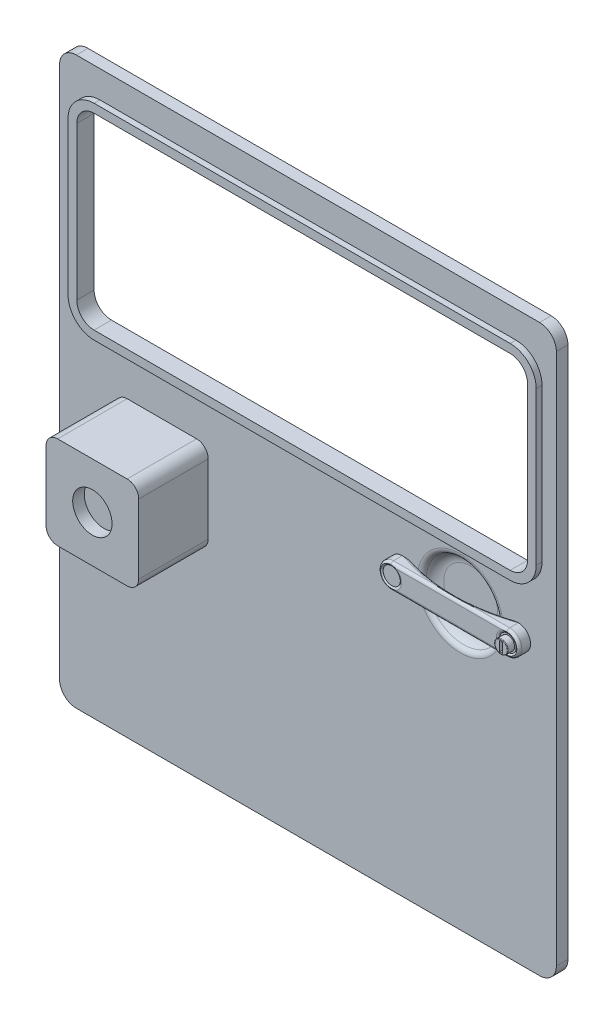
SolidWorks part; units mm, degrees
material "AISI 347 Annealed Stainless Steel (SS)"
ref_plane "Front Plane" through (0, 0, 0) normal (0, 0, 1) x (1, 0, 0)
ref_plane "Top Plane" through (0, 0, 0) normal (0, 1, 0) x (1, 0, 0)
ref_plane "Right Plane" through (0, 0, 0) normal (1, 0, 0) x (0, 0, -1)
sketch "Sketch1" plane through (0, 0, 0) normal (0, 0, 1) x (1, 0, 0)
  line L0 (400, 489.5011) -> (-400, 489.5011)
  line L1 (430, -459.5316) -> (430, 459.5316)
  line L2 (-400, -489.5011) -> (400, -489.5011)
  line L3 (-430, 459.5316) -> (-430, -459.5316)
  line L4 (400, 488.5011) -> (-400, 488.5011)
  line L5 (-429, 459.5316) -> (-429, -459.5316)
  line L6 (-400, -488.5011) -> (400, -488.5011)
  line L7 (429, -459.5316) -> (429, 459.5316)
  ellipse E0 centre (400, 459.5316) end of major axis (370, 459.5316) minor radius 29.9695 (430, 459.5316) -> (400, 489.5011) ccw
  ellipse E1 centre (400, -459.5316) end of major axis (430, -459.5316) minor radius 29.9695 (400, -489.5011) -> (430, -459.5316) ccw
  ellipse E2 centre (-400, -459.5316) end of major axis (-370, -459.5316) minor radius 29.9695 (-430, -459.5316) -> (-400, -489.5011) ccw
  ellipse E3 centre (-400, 459.5316) end of major axis (-370, 459.5316) minor radius 29.9695 (-400, 489.5011) -> (-430, 459.5316) ccw
  spline S0 degree 1 poles (-400, 488.5011) (-429, 459.5316) knots 0 0 1 1 construction
  spline S1 degree 1 poles (-429, -459.5316) (-400, -488.5011) knots 0 0 1 1 construction
  spline S2 degree 1 poles (400, -488.5011) (429, -459.5316) knots 0 0 1 1 construction
  spline S3 degree 1 poles (429, 459.5316) (400, 488.5011) knots 0 0 1 1 construction
  spline S4 degree 3 poles (-400, 488.5011) (-401.895, 488.5011) (-405.6955, 488.1273) (-412.9948, 485.9167) (-421.0414, 480.5501) (-426.4132, 472.512) (-428.6259, 465.2207) (-429, 461.4246) (-429, 459.5316) knots 1.570796 1.570796 1.570796 1.570796 1.767146 1.963495 2.356194 2.748894 2.945243 3.141593 3.141593 3.141593 3.141593
  spline S5 degree 3 poles (-429, -459.5316) (-429, -461.4246) (-428.6259, -465.2207) (-426.4132, -472.512) (-421.0414, -480.5501) (-412.9948, -485.9167) (-405.6955, -488.1273) (-401.895, -488.5011) (-400, -488.5011) knots 3.141593 3.141593 3.141593 3.141593 3.337942 3.534292 3.926991 4.31969 4.516039 4.712389 4.712389 4.712389 4.712389
  spline S6 degree 3 poles (400, -488.5011) (401.895, -488.5011) (405.6955, -488.1273) (412.9948, -485.9167) (421.0414, -480.5501) (426.4132, -472.512) (428.6259, -465.2207) (429, -461.4246) (429, -459.5316) knots -1.570796 -1.570796 -1.570796 -1.570796 -1.374447 -1.178097 -0.785398 -0.392699 -0.19635 0 0 0 0
  spline S7 degree 3 poles (429, 459.5316) (429, 461.4246) (428.6259, 465.2207) (426.4132, 472.512) (421.0414, 480.5501) (412.9948, 485.9167) (405.6955, 488.1273) (401.895, 488.5011) (400, 488.5011) knots -3.141593 -3.141593 -3.141593 -3.141593 -2.945243 -2.748894 -2.356194 -1.963495 -1.767146 -1.570796 -1.570796 -1.570796 -1.570796
  dimension "D1" = 1
extrude "Boss-Extrude1" add sketch "Sketch1" along normal mid plane 20 contours L7 S7 L4 S4 L5 S5 L6 S6
sketch "Sketch2" plane through (0, 0, 10) normal (0, 0, 1) x (1, 0, 0)
  line L0 (0, 488.5011) -> (0, 264.5322) construction
  line L1 (400, 488.5011) -> (-400, 488.5011) construction
  line L3 (359.2197, 102.3905) -> (-359.2197, 102.3905)
  line L4 (389.2197, 132.3905) -> (389.2197, 396.6739)
  line L5 (359.2197, 426.6739) -> (-359.2197, 426.6739)
  line L6 (-389.2197, 132.3905) -> (-389.2197, 396.6739)
  line L7 (389.2197, 102.3905) -> (-389.2197, 426.6739) construction
  line L8 (389.2197, 426.6739) -> (-389.2197, 102.3905) construction
  arc A0 (-359.2197, 102.3905) -> (-389.2197, 132.3905) centre (-359.2197, 132.3905) cw
  arc A1 (389.2197, 396.6739) -> (359.2197, 426.6739) centre (359.2197, 396.6739) ccw
  arc A2 (359.2197, 102.3905) -> (389.2197, 132.3905) centre (359.2197, 132.3905) ccw
  arc A3 (-359.2197, 426.6739) -> (-389.2197, 396.6739) centre (-359.2197, 396.6739) ccw
  dimension "D1" = 30
extrude "Cut-Extrude1" cut sketch "Sketch2" against normal through all
sketch "Sketch4" plane through (0, 0, 10) normal (0, 0, 1) x (1, 0, 0)
  line L1 (-192.2469, -141.7056) -> (-312.2469, -141.7056)
  line L2 (-172.2469, -121.7056) -> (-172.2469, -1.7056)
  line L3 (-192.2469, 18.2944) -> (-312.2469, 18.2944)
  line L4 (-332.2469, -121.7056) -> (-332.2469, -1.7056)
  line L5 (-172.2469, -141.7056) -> (-332.2469, 18.2944) construction
  line L6 (-172.2469, 18.2944) -> (-332.2469, -141.7056) construction
  arc A0 (-312.2469, -141.7056) -> (-332.2469, -121.7056) centre (-312.2469, -121.7056) cw
  arc A1 (-172.2469, -1.7056) -> (-192.2469, 18.2944) centre (-192.2469, -1.7056) ccw
  arc A2 (-192.2469, -141.7056) -> (-172.2469, -121.7056) centre (-192.2469, -121.7056) ccw
  arc A3 (-312.2469, 18.2944) -> (-332.2469, -1.7056) centre (-312.2469, -1.7056) ccw
  point P0 (-252.2469, -61.7056)
  point P5 (-252.2469, -61.7056)
  dimension "D3" = 20
  dimension "D1" = 160
  dimension "D2" = 160
extrude "Boss-Extrude2" add sketch "Sketch4" along normal blind 120
sketch "Sketch5" plane through (0, 0, 130) normal (0, 0, 1) x (1, 0, 0)
  line L0 (-252.2469, 18.2944) -> (-252.2469, -141.7056) construction
  line L1 (-192.2469, 18.2944) -> (-312.2469, 18.2944) construction
  line L2 (-312.2469, -141.7056) -> (-192.2469, -141.7056) construction
  circle A0 centre (-252.2469, -61.7056) radius 33.9854
extrude "Cut-Extrude2" cut sketch "Sketch5" against normal blind 20
sketch "Sketch6" plane through (0, 0, 10) normal (0, 0, 1) x (1, 0, 0)
  line L0 (162.7399, 0) -> (363.4525, 0) construction
  line L1 (162.7399, 21.0206) -> (363.4525, 21.0206)
  line L2 (162.7399, -21.0206) -> (363.4525, -21.0206)
  arc A0 (162.7399, 21.0206) -> (162.7399, -21.0206) centre (162.7399, 0) ccw
  arc A1 (363.4525, -21.0206) -> (363.4525, 21.0206) centre (363.4525, 0) ccw
  point P3 (263.0962, 0)
  point P8 (162.7399, 0)
  point P9 (363.4525, 0)
extrude "Boss-Extrude3" add sketch "Sketch6" along normal blind 20
sketch "Sketch9" plane through (0, 0, 10) normal (0, 0, 1) x (1, 0, 0)
  line L0 (263.0962, 21.0206) -> (263.0962, -21.0206) construction
  line L1 (363.4525, 21.0206) -> (162.7399, 21.0206) construction
  line L2 (162.7399, -21.0206) -> (363.4525, -21.0206) construction
  circle A0 centre (263.0962, 0) radius 66.5209
extrude "Cut-Extrude5" cut sketch "Sketch9" against normal blind 18
sketch "Sketch10" plane through (0, 21.0206, 0) normal (0, 1, 0) x (1, 0, 0)
  line L0 (199.9839, -10) -> (162.7399, -10) construction
  line L1 (363.4525, -10) -> (326.2085, -10) construction
  line L2 (181.3619, -10) -> (348.7014, -10)
  arc A0 (181.3619, -10) -> (348.7014, -10) centre (265.0317, 269.1036) ccw
  point P3 (348.7014, -10)
extrude "Cut-Extrude6" cut sketch "Sketch10" against normal blind 60
fillet "Fillet1" radius 20 1 edges at (329.6171, 0, -8)
fillet "Fillet2" radius 10 1 edges at (329.6171, 0, 10)
sketch "Sketch11" plane through (0, 0, 30) normal (0, 0, 1) x (1, 0, 0)
  circle A0 centre (162.7399, 0) radius 14.8405
  circle A1 centre (363.4525, 0) radius 14.252
extrude "Cut-Extrude7" cut sketch "Sketch11" against normal blind 2
sketch "Sketch12" plane through (0, 0, 28) normal (0, 0, 1) x (1, 0, 0)
  circle A0 centre (363.4525, 0) radius 11.538
extrude "Boss-Extrude4" add sketch "Sketch12" along normal blind 12
sketch "Sketch13" plane through (0, 0, 40) normal (0, 0, 1) x (1, 0, 0)
  line L1 (365.8065, -8.5434) -> (361.0985, -8.5434)
  line L2 (365.8065, -8.5434) -> (365.8065, 8.5434)
  line L3 (365.8065, 8.5434) -> (361.0985, 8.5434)
  line L4 (361.0985, -8.5434) -> (361.0985, 8.5434)
  line L5 (365.8065, -8.5434) -> (361.0985, 8.5434) construction
  line L6 (365.8065, 8.5434) -> (361.0985, -8.5434) construction
  point P0 (363.4525, 0)
extrude "Cut-Extrude8" cut sketch "Sketch13" against normal blind 12
fillet "Fillet3" radius 5 8 edges at (263.0962, 21.0206, 30) (384.4731, 0, 30) (263.0962, -21.0206, 30) (141.7194, 0, 30) (377.7045, 0, 30) (177.5804, 0, 30) (265.0317, -21.0206, 22.2715) (265.0317, 21.0206, 22.2715)
fillet "Fillet4" radius 1 1 edges at (374.9905, 0, 40)
sketch "Sketch14" plane through (0, 0, 10) normal (0, 0, 1) x (1, 0, 0)
  line L20 (389.2197, 132.3905) -> (389.2197, 396.6739) construction
  line L21 (-359.2197, 102.3905) -> (359.2197, 102.3905) construction
  line L22 (-389.2197, 396.6739) -> (-389.2197, 132.3905) construction
  line L23 (359.2197, 426.6739) -> (-359.2197, 426.6739) construction
  line L24 (404.2197, 132.3905) -> (404.2197, 396.6739)
  line L25 (-359.2197, 87.3905) -> (359.2197, 87.3905)
  line L26 (-404.2197, 396.6739) -> (-404.2197, 132.3905)
  line L27 (359.2197, 441.6739) -> (-359.2197, 441.6739)
  line L28 (404.2197, 132.3905) -> (404.2197, 396.6739)
  line L29 (-359.2197, 87.3905) -> (359.2197, 87.3905)
  line L30 (-404.2197, 396.6739) -> (-404.2197, 132.3905)
  line L31 (359.2197, 441.6739) -> (-359.2197, 441.6739)
  line L32 (389.2197, 132.3905) -> (389.2197, 396.6739)
  line L33 (-359.2197, 102.3905) -> (359.2197, 102.3905)
  line L34 (-389.2197, 396.6739) -> (-389.2197, 132.3905)
  line L35 (359.2197, 426.6739) -> (-359.2197, 426.6739)
  arc A17 (389.2197, 396.6739) -> (359.2197, 426.6739) centre (359.2197, 396.6739) ccw construction
  arc A18 (359.2197, 102.3905) -> (389.2197, 132.3905) centre (359.2197, 132.3905) ccw construction
  arc A19 (-389.2197, 132.3905) -> (-359.2197, 102.3905) centre (-359.2197, 132.3905) ccw construction
  arc A20 (404.2197, 396.6739) -> (359.2197, 441.6739) centre (359.2197, 396.6739) ccw
  arc A21 (359.2197, 87.3905) -> (404.2197, 132.3905) centre (359.2197, 132.3905) ccw
  arc A22 (-404.2197, 132.3905) -> (-359.2197, 87.3905) centre (-359.2197, 132.3905) ccw
  arc A23 (-359.2197, 441.6739) -> (-404.2197, 396.6739) centre (-359.2197, 396.6739) ccw
  arc A24 (404.2197, 396.6739) -> (359.2197, 441.6739) centre (359.2197, 396.6739) ccw
  arc A25 (359.2197, 87.3905) -> (404.2197, 132.3905) centre (359.2197, 132.3905) ccw
  arc A26 (-404.2197, 132.3905) -> (-359.2197, 87.3905) centre (-359.2197, 132.3905) ccw
  arc A27 (-359.2197, 441.6739) -> (-404.2197, 396.6739) centre (-359.2197, 396.6739) ccw
  arc A28 (-359.2197, 426.6739) -> (-389.2197, 396.6739) centre (-359.2197, 396.6739) ccw construction
  arc A29 (389.2197, 396.6739) -> (359.2197, 426.6739) centre (359.2197, 396.6739) ccw
  arc A30 (359.2197, 102.3905) -> (389.2197, 132.3905) centre (359.2197, 132.3905) ccw
  arc A31 (-389.2197, 132.3905) -> (-359.2197, 102.3905) centre (-359.2197, 132.3905) ccw
  arc A32 (-359.2197, 426.6739) -> (-389.2197, 396.6739) centre (-359.2197, 396.6739) ccw
  dimension "D1" = 15
extrude "Boss-Extrude5" add sketch "Sketch14" along normal blind 10
